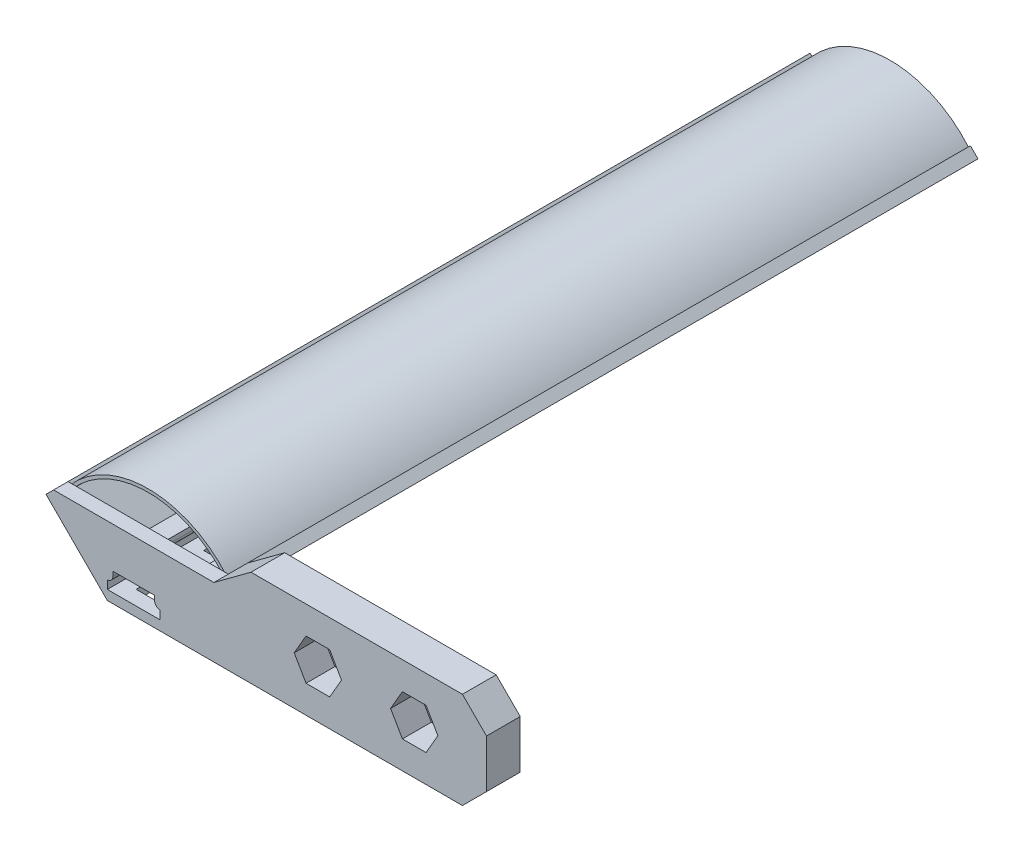
SolidWorks part; units mm, degrees
ref_plane "Front Plane" through (0, 0, 0) normal (0, 0, 1) x (1, 0, 0)
ref_plane "Top Plane" through (0, 0, 0) normal (0, 1, 0) x (1, 0, 0)
ref_plane "Right Plane" through (0, 0, 0) normal (1, 0, 0) x (0, 0, -1)
sketch "Sketch1" plane through (0, 0, 0) normal (0, 0, 1) x (1, 0, 0)
  line L0 (5.48, 0) -> (18.21, 12.73)
  line L1 (18.21, 12.73) -> (16.635, 14.305)
  line L2 (16.635, 14.305) -> (16.2107, 13.8807)
  line L3 (16.2107, 13.8807) -> (17.0593, 13.0322)
  line L4 (17.0593, 13.0322) -> (16.5996, 12.5726)
  line L5 (16.5996, 12.5726) -> (15.7511, 13.4211)
  line L6 (15.7511, 13.4211) -> (8.18, 5.85)
  line L7 (8.18, 5.85) -> (4.33, 5.85)
  line L8 (4.33, 5.85) -> (4.33, 3.73)
  line L9 (4.33, 3.73) -> (5.48, 3.73)
  line L10 (5.48, 3.73) -> (5.48, 2)
  line L11 (5.48, 2) -> (-5.48, 2)
  line L13 (-5.48, 0) -> (5.48, 0)
  line L14 (-5.48, 3.73) -> (-5.48, 2)
  line L15 (-4.33, 3.73) -> (-5.48, 3.73)
  line L16 (-4.33, 5.85) -> (-4.33, 3.73)
  line L17 (-8.18, 5.85) -> (-4.33, 5.85)
  line L18 (-15.7511, 13.4211) -> (-8.18, 5.85)
  line L19 (-16.5996, 12.5726) -> (-15.7511, 13.4211)
  line L20 (-17.0593, 13.0322) -> (-16.5996, 12.5726)
  line L21 (-16.2107, 13.8807) -> (-17.0593, 13.0322)
  line L22 (-16.635, 14.305) -> (-16.2107, 13.8807)
  line L23 (-18.21, 12.73) -> (-16.635, 14.305)
  line L24 (-5.48, 0) -> (-18.21, 12.73)
  dimension "D2" = 2
  dimension "D3" = 1.73
  dimension "D4" = 3.85
  dimension "D5" = 1.15
  dimension "D6" = 2.12
  dimension "D7" = 12.73
  dimension "D8" = 12.73
  dimension "D9" = 0.65
  dimension "D10" = 1.2
  dimension "D11" = 0.6
extrude "Boss-Extrude1" add sketch "Sketch1" along normal blind 157
sketch "Sketch2" plane through (0, 2, 0) normal (0, 1, 0) x (1, 0, 0)
  line L0 (5.48, -157) -> (-5.48, -157) construction
  line L1 (-2.5, -2) -> (2.5, -2)
  line L2 (-2.5, -2) -> (-2.5, -7)
  line L3 (-2.5, -7) -> (2.5, -7)
  line L4 (2.5, -2) -> (2.5, -7)
  line L5 (-2.5, -2) -> (2.5, -7) construction
  line L6 (-2.5, -7) -> (2.5, -2) construction
  line L7 (-2.5, -149) -> (2.5, -149)
  line L8 (-2.5, -149) -> (-2.5, -154)
  line L9 (-2.5, -154) -> (2.5, -154)
  line L10 (2.5, -149) -> (2.5, -154)
  line L11 (-2.5, -149) -> (2.5, -154) construction
  line L12 (-2.5, -154) -> (2.5, -149) construction
  point P0 (0, -4.5)
  point P8 (0, -151.5)
  dimension "D1" = 3
  dimension "D2" = 5
  dimension "D3" = 2
extrude "Cut-Extrude1" cut sketch "Sketch2" against normal blind 157
sketch "Sketch3" plane through (0, 2, 0) normal (0, 1, 0) x (1, 0, 0)
  line L114 (18.21, -78.5) -> (-18.21, -78.5) construction
  line L115 (18.21, -157) -> (18.21, 0) construction
  line L116 (-18.21, -157) -> (-18.21, 0) construction
  line L117 (2.5, -154) -> (2.5, -149) construction
  line L118 (-2.5, -142) -> (2.5, -142)
  line L119 (-2.5, -142) -> (-2.5, -147)
  line L120 (-2.5, -147) -> (2.5, -147)
  line L121 (2.5, -142) -> (2.5, -147)
  line L122 (-2.5, -142) -> (2.5, -147) construction
  line L123 (-2.5, -147) -> (2.5, -142) construction
  line L124 (-2.5, -135) -> (2.5, -135)
  line L125 (-2.5, -135) -> (-2.5, -140)
  line L126 (-2.5, -140) -> (2.5, -140)
  line L127 (2.5, -135) -> (2.5, -140)
  line L128 (-2.5, -135) -> (2.5, -140) construction
  line L129 (-2.5, -140) -> (2.5, -135) construction
  line L130 (-2.5, -128) -> (2.5, -128)
  line L131 (-2.5, -128) -> (-2.5, -133)
  line L132 (-2.5, -133) -> (2.5, -133)
  line L133 (2.5, -128) -> (2.5, -133)
  line L134 (-2.5, -128) -> (2.5, -133) construction
  line L135 (-2.5, -133) -> (2.5, -128) construction
  line L136 (-2.5, -86) -> (2.5, -86)
  line L137 (-2.5, -86) -> (-2.5, -91)
  line L138 (-2.5, -91) -> (2.5, -91)
  line L139 (2.5, -86) -> (2.5, -91)
  line L140 (-2.5, -86) -> (2.5, -91) construction
  line L141 (-2.5, -91) -> (2.5, -86) construction
  line L142 (-2.5, -79) -> (2.5, -79)
  line L143 (-2.5, -79) -> (-2.5, -84)
  line L144 (-2.5, -84) -> (2.5, -84)
  line L145 (2.5, -79) -> (2.5, -84)
  line L146 (-2.5, -79) -> (2.5, -84) construction
  line L147 (-2.5, -84) -> (2.5, -79) construction
  line L148 (-2.5, -93) -> (2.5, -93)
  line L149 (-2.5, -93) -> (-2.5, -98)
  line L150 (-2.5, -98) -> (2.5, -98)
  line L151 (2.5, -93) -> (2.5, -98)
  line L152 (-2.5, -93) -> (2.5, -98) construction
  line L153 (-2.5, -98) -> (2.5, -93) construction
  line L154 (-2.5, -100) -> (2.5, -100)
  line L155 (-2.5, -100) -> (-2.5, -105)
  line L156 (-2.5, -105) -> (2.5, -105)
  line L157 (2.5, -100) -> (2.5, -105)
  line L158 (-2.5, -100) -> (2.5, -105) construction
  line L159 (-2.5, -105) -> (2.5, -100) construction
  line L160 (-2.5, -107) -> (2.5, -107)
  line L161 (-2.5, -107) -> (-2.5, -112)
  line L162 (-2.5, -112) -> (2.5, -112)
  line L163 (2.5, -107) -> (2.5, -112)
  line L164 (-2.5, -107) -> (2.5, -112) construction
  line L165 (-2.5, -112) -> (2.5, -107) construction
  line L166 (-2.5, -114) -> (2.5, -114)
  line L167 (-2.5, -114) -> (-2.5, -119)
  line L168 (-2.5, -119) -> (2.5, -119)
  line L169 (2.5, -114) -> (2.5, -119)
  line L170 (-2.5, -114) -> (2.5, -119) construction
  line L171 (-2.5, -119) -> (2.5, -114) construction
  line L172 (-2.5, -121) -> (2.5, -121)
  line L173 (-2.5, -121) -> (-2.5, -126)
  line L174 (-2.5, -126) -> (2.5, -126)
  line L175 (2.5, -121) -> (2.5, -126)
  line L176 (-2.5, -121) -> (2.5, -126) construction
  line L177 (-2.5, -126) -> (2.5, -121) construction
  line L178 (2.5, -149) -> (-2.5, -149) construction
  line L179 (-2.5, -31) -> (2.5, -36) construction
  line L180 (-2.5, -36) -> (2.5, -31) construction
  line L181 (-2.5, -38) -> (2.5, -43) construction
  line L182 (-2.5, -43) -> (2.5, -38) construction
  line L183 (-2.5, -45) -> (2.5, -50) construction
  line L184 (-2.5, -50) -> (2.5, -45) construction
  line L185 (-2.5, -52) -> (2.5, -57) construction
  line L186 (-2.5, -57) -> (2.5, -52) construction
  line L187 (-2.5, -59) -> (2.5, -64) construction
  line L188 (-2.5, -64) -> (2.5, -59) construction
  line L189 (-2.5, -73) -> (2.5, -78) construction
  line L190 (-2.5, -78) -> (2.5, -73) construction
  line L191 (-2.5, -66) -> (2.5, -71) construction
  line L192 (-2.5, -71) -> (2.5, -66) construction
  line L193 (-2.5, -24) -> (2.5, -29) construction
  line L194 (-2.5, -29) -> (2.5, -24) construction
  line L195 (-2.5, -17) -> (2.5, -22) construction
  line L196 (-2.5, -22) -> (2.5, -17) construction
  line L197 (-2.5, -10) -> (2.5, -15) construction
  line L198 (-2.5, -15) -> (2.5, -10) construction
  line L199 (2.5, -36) -> (2.5, -31)
  line L200 (-2.5, -31) -> (2.5, -31)
  line L201 (-2.5, -36) -> (-2.5, -31)
  line L202 (-2.5, -36) -> (2.5, -36)
  line L203 (2.5, -43) -> (2.5, -38)
  line L204 (-2.5, -38) -> (2.5, -38)
  line L205 (-2.5, -43) -> (-2.5, -38)
  line L206 (-2.5, -43) -> (2.5, -43)
  line L207 (2.5, -50) -> (2.5, -45)
  line L208 (-2.5, -45) -> (2.5, -45)
  line L209 (-2.5, -50) -> (-2.5, -45)
  line L210 (-2.5, -50) -> (2.5, -50)
  line L211 (2.5, -57) -> (2.5, -52)
  line L212 (-2.5, -52) -> (2.5, -52)
  line L213 (-2.5, -57) -> (-2.5, -52)
  line L214 (-2.5, -57) -> (2.5, -57)
  line L215 (2.5, -64) -> (2.5, -59)
  line L216 (-2.5, -59) -> (2.5, -59)
  line L217 (-2.5, -64) -> (-2.5, -59)
  line L218 (-2.5, -64) -> (2.5, -64)
  line L219 (2.5, -78) -> (2.5, -73)
  line L220 (-2.5, -73) -> (2.5, -73)
  line L221 (-2.5, -78) -> (-2.5, -73)
  line L222 (-2.5, -78) -> (2.5, -78)
  line L223 (2.5, -71) -> (2.5, -66)
  line L224 (-2.5, -66) -> (2.5, -66)
  line L225 (-2.5, -71) -> (-2.5, -66)
  line L226 (-2.5, -71) -> (2.5, -71)
  line L227 (2.5, -29) -> (2.5, -24)
  line L228 (-2.5, -24) -> (2.5, -24)
  line L229 (-2.5, -29) -> (-2.5, -24)
  line L230 (-2.5, -29) -> (2.5, -29)
  line L231 (2.5, -22) -> (2.5, -17)
  line L232 (-2.5, -17) -> (2.5, -17)
  line L233 (-2.5, -22) -> (-2.5, -17)
  line L234 (-2.5, -22) -> (2.5, -22)
  line L235 (2.5, -15) -> (2.5, -10)
  line L236 (-2.5, -10) -> (2.5, -10)
  line L237 (-2.5, -15) -> (-2.5, -10)
  line L238 (-2.5, -15) -> (2.5, -15)
  point P7 (0, -144.5)
  point P12 (0, -137.5)
  point P17 (0, -130.5)
  point P22 (0, -88.5)
  point P27 (0, -81.5)
  point P32 (0, -95.5)
  point P37 (0, -102.5)
  point P42 (0, -109.5)
  point P47 (0, -116.5)
  point P52 (0, -123.5)
  point P102 (0, -33.5)
  point P103 (0, -40.5)
  point P104 (0, -47.5)
  point P105 (0, -54.5)
  point P106 (0, -61.5)
  point P107 (0, -75.5)
  point P108 (0, -68.5)
  point P109 (0, -26.5)
  point P110 (0, -19.5)
  point P111 (0, -12.5)
  dimension "D1" = 5
  dimension "D2" = 2
  dimension "D3" = 2
  dimension "D4" = 2
  dimension "D5" = 2
  dimension "D6" = 2
  dimension "D7" = 2
  dimension "D8" = 2
  dimension "D9" = 2
  dimension "D10" = 2
  dimension "D11" = 2
extrude "Cut-Extrude2" cut sketch "Sketch3" against normal blind 157
fillet "Fillet1" radius 1.2 2 edges at (4.33, 3.73, 78.5) (-4.33, 3.73, 78.5)
sketch "Sketch4" plane through (0, 0, 157) normal (0, 0, 1) x (1, 0, 0)
  line L0 (-16.635, 14.305) -> (16.635, 14.305)
  line L1 (16.635, 14.305) -> (18.21, 12.73)
  line L2 (18.21, 12.73) -> (5.48, 0)
  line L3 (5.48, 0) -> (-5.48, 0)
  line L4 (-5.48, 0) -> (-18.21, 12.73)
  line L5 (-18.21, 12.73) -> (-16.635, 14.305)
  line L6 (-5.48, 3.925) -> (5.48, 3.925) construction
  line L7 (-5.48, 5.85) -> (5.48, 5.85)
  line L8 (-5.48, 2) -> (5.48, 2)
  line L9 (5.48, 2) -> (-5.48, 2) construction
  line L10 (-4.33, 5.85) -> (-8.18, 5.85) construction
  arc A0 (-5.48, 5.85) -> (-5.48, 2) centre (-5.48, 3.925) ccw
  arc A1 (5.48, 2) -> (5.48, 5.85) centre (5.48, 3.925) ccw
  point P14 (0, 3.925)
extrude "Boss-Extrude2" add sketch "Sketch4" against normal blind 3
sketch "Sketch5" plane through (0, 0, 157) normal (0, 0, 1) x (1, 0, 0)
  line L0 (23.21, 0) -> (68.21, 0)
  line L1 (68.21, 0) -> (73.21, 5)
  line L2 (73.21, 5) -> (73.21, 15)
  line L3 (73.21, 15) -> (68.21, 20)
  line L4 (68.21, 20) -> (24.3333, 20)
  line L5 (24.3333, 20) -> (16.635, 14.305)
  line L6 (18.21, 12.73) -> (5.48, 0)
  line L7 (5.48, 0) -> (23.21, 0)
  arc A0 (16.635, 14.305) -> (18.21, 12.73) centre (22.6874, 18.7824) ccw
  dimension "D1" = 45
  dimension "D2" = 5
  dimension "D3" = 5
  dimension "D4" = 10
  dimension "D5" = 5
  dimension "D6" = 20
extrude "Boss-Extrude3" add sketch "Sketch5" against normal blind 7
sketch "Sketch6" plane through (0, 0, 157) normal (0, 0, 1) x (1, 0, 0)
  line L0 (73.21, 5) -> (73.21, 15) construction
  line L1 (73.21, 10) -> (16.3078, 10) construction
  circle A0 centre (38.21, 10) radius 2.75
  circle A1 centre (58.21, 10) radius 2.75
  dimension "D1" = 15
  dimension "D2" = 20
  dimension "D3" = 5.5
  dimension "D4" = 5.5
extrude "Cut-Extrude3" cut sketch "Sketch6" against normal through all
sketch "Sketch7" plane through (0, 0, 157) normal (0, 0, 1) x (1, 0, 0)
  line L1 (43.1175, 10) -> (40.6637, 14.25)
  line L2 (40.6637, 14.25) -> (35.7563, 14.25)
  line L3 (35.7563, 14.25) -> (33.3025, 10)
  line L4 (33.3025, 10) -> (35.7563, 5.75)
  line L5 (35.7563, 5.75) -> (40.6637, 5.75)
  line L6 (40.6637, 5.75) -> (43.1175, 10)
  line L7 (63.1175, 10) -> (60.6637, 14.25)
  line L8 (60.6637, 14.25) -> (55.7563, 14.25)
  line L9 (55.7563, 14.25) -> (53.3025, 10)
  line L10 (53.3025, 10) -> (55.7563, 5.75)
  line L11 (55.7563, 5.75) -> (60.6637, 5.75)
  line L12 (60.6637, 5.75) -> (63.1175, 10)
  circle A0 centre (38.21, 10) radius 4.25 construction
  circle A1 centre (58.21, 10) radius 4.25 construction
  dimension "D1" = 8.5
extrude "Cut-Extrude4" cut sketch "Sketch7" against normal offset from surface (6 mm away) 1 up to face at (40.96, 10, 150)
sketch "Sketch8" plane through (0, 0, 0) normal (0, 0, -1) x (-1, 0, 0)
  line L0 (15.7511, 13.4211) -> (16.2107, 13.8807)
  line L1 (-16.2107, 13.8807) -> (-15.7511, 13.4211)
  arc A0 (16.2107, 13.8807) -> (-16.2107, 13.8807) centre (0, 0) ccw
  arc A1 (15.7511, 13.4211) -> (-15.7511, 13.4211) centre (0, 0) ccw
extrude "Boss-Extrude4" add sketch "Sketch8" against normal up to surface (154 mm away) separate body up to face at (0, 11.2731, 154)
